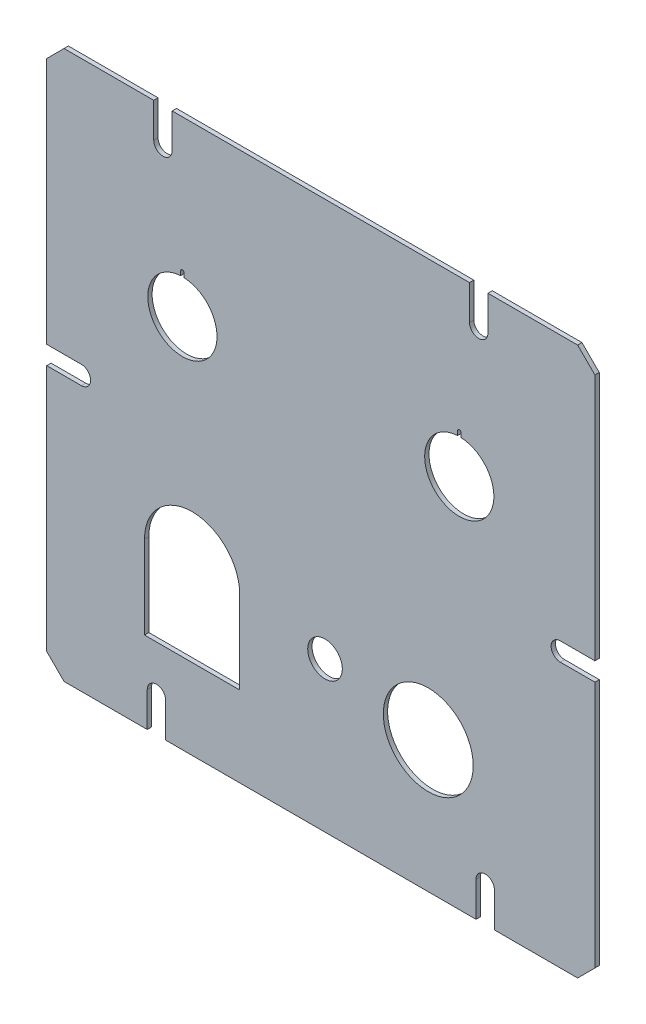
SolidWorks part; units mm, degrees
material "PE High Density"
ref_plane "Front" through (0, 0, 0) normal (0, 0, 1) x (1, 0, 0)
ref_plane "Top" through (0, 0, 0) normal (0, 1, 0) x (1, 0, 0)
ref_plane "Right" through (0, 0, 0) normal (1, 0, 0) x (0, 0, -1)
ref_axis "Axis1" through (0, 0, 55) along (0, 0, -1)
sketch "Sketch1" plane through (0, 0, 0) normal (0, 0, 1) x (1, 0, 0)
  line L1 (-100.584, 100.584) -> (100.584, 100.584)
  line L2 (-100.584, 100.584) -> (-100.584, -100.584)
  line L3 (-100.584, -100.584) -> (100.584, -100.584)
  line L4 (100.584, 100.584) -> (100.584, -100.584)
  line L5 (-100.584, 100.584) -> (100.584, -100.584) construction
  line L6 (-100.584, -100.584) -> (100.584, 100.584) construction
  point P0 (0, 0)
  dimension "D1" = 201.168
extrude "Boss-Extrude1" add sketch "Sketch1" along normal blind 1.5875
sketch "Sketch2" plane through (0, 0, 1.5875) normal (0, 0, 1) x (1, 0, 0)
  line L0 (100.584, -100.584) -> (100.584, 100.584) construction
  line L1 (100.584, 100.584) -> (-100.584, 100.584) construction
  circle A0 centre (-47.244, -40.5765) radius 17.4625
  circle A1 centre (39.4206, -52.284) radius 16.5
  dimension "D1" = 33
  dimension "D6" = 34.925
  dimension "D2" = 61.1634
  dimension "D3" = 147.828
  dimension "D4" = 141.1605
  dimension "D5" = 152.868
extrude "Cut-Extrude1" cut sketch "Sketch2" against normal up to next
hole_wizard "1/4 Clearance Hole1" positions "Sketch3" profile "Sketch4" hole size "1/4" standard "ANSI Inch" end condition up to next
sketch "Sketch3" plane through (0, 0, 1.5875) normal (0, 0, 1) x (1, 0, 0)
  line L0 (0, 100.584) -> (0, -100.584) construction
  line L1 (100.584, 100.584) -> (-100.584, 100.584) construction
  line L2 (-100.584, -100.584) -> (100.584, -100.584) construction
  line L4 (-100.584, 0) -> (100.584, 0) construction
  line L5 (-100.584, 100.584) -> (-100.584, -100.584) construction
  line L6 (100.584, -100.584) -> (100.584, 100.584) construction
  line L8 (-57.9437, 87.884) -> (57.9438, 87.884) construction
  line L10 (-60.325, -87.884) -> (60.325, -87.884) construction
  point P0 (-57.9437, 87.884)
  point P2 (57.9438, 87.884)
  point P4 (87.884, 0)
  point P6 (-87.884, 0)
  point P8 (-60.325, -87.884)
  point P10 (60.325, -87.884)
  dimension "D1" = 12.7
  dimension "D2" = 115.8875
  dimension "D3" = 12.7
  dimension "D4" = 120.65
  dimension "D5" = 12.7
sketch "Sketch4" plane through (-57.9437, 87.884, 1.5875) normal (1, 0, 0) x (0, -1, 0)
  line L0 (0, 0) -> (0, 1.5875)
  line L1 (0, 1.5875) -> (3.3782, 1.5875)
  line L2 (3.3782, 1.5875) -> (3.3782, 0)
  line L5 (3.3782, 0) -> (0, 0)
  line L11 (0, -6.35) -> (0, 107.95) construction
  dimension "Thru Hole Dia." = 6.7564
  dimension "Thru Hole Depth" = 1.5875
chamfer "Chamfer1" distance 6.35 angle 45 4 edges at (-100.584, -100.584, 0.7937) (100.584, -100.584, 0.7937) (100.584, 100.584, 0.7937) (-100.584, 100.584, 0.7937)
sketch "Sketch5" plane through (0, 0, 0) normal (0, 0, -1) x (-1, 0, 0)
  line L0 (29.7815, -40.5765) -> (29.7815, -71.0565)
  line L1 (29.7815, -71.0565) -> (64.7065, -71.0565)
  line L2 (64.7065, -71.0565) -> (64.7065, -40.5765)
  circle A0 centre (47.244, -40.5765) radius 17.4625 construction
  arc A1 (29.7815, -40.5765) -> (64.7065, -40.5765) centre (47.244, -40.5765) ccw
  dimension "D1" = 30.48
extrude "Cut-Extrude3" cut sketch "Sketch5" against normal up to next
sketch "Sketch6" plane through (0, 0, 0) normal (0, 0, -1) x (-1, 0, 0)
  line L0 (-50.8, 37.084) -> (50.8, 37.084) construction
  line L1 (0, 100.584) -> (0, -100.584) construction
  line L2 (-94.234, 100.584) -> (94.234, 100.584) construction
  line L3 (94.234, -100.584) -> (-94.234, -100.584) construction
  line L4 (-50.8, 37.084) -> (-50.8, 51.308) construction
  line L5 (50.8, 37.084) -> (50.8, 51.308) construction
  line L6 (-50.8, 51.308) -> (50.8, 51.308) construction
  line L7 (-50.165, 49.7681) -> (-50.165, 51.308)
  line L8 (51.435, 49.7681) -> (51.435, 51.308)
  line L9 (-51.435, 49.7681) -> (-51.435, 51.308)
  line L10 (50.165, 49.7681) -> (50.165, 51.308)
  line L11 (-51.435, 37.084) -> (-51.435, 51.308) construction
  line L12 (-50.165, 37.084) -> (-50.165, 51.308) construction
  line L13 (50.165, 37.084) -> (50.165, 51.308) construction
  line L14 (51.435, 37.084) -> (51.435, 51.308) construction
  arc A0 (-51.435, 49.7681) -> (-50.165, 49.7681) centre (-50.8, 37.084) ccw
  arc A1 (50.165, 49.7681) -> (51.435, 49.7681) centre (50.8, 37.084) ccw
  arc A2 (-51.435, 51.308) -> (-50.165, 51.308) centre (-50.8, 51.308) cw
  arc A3 (50.165, 51.308) -> (51.435, 51.308) centre (50.8, 51.308) cw
  dimension "D2" = 25.4
  dimension "D1" = 101.6
  dimension "D3" = 63.5
  dimension "D4" = 0.635
  dimension "D6" = 14.224
  dimension "D5" = 0.635
extrude "Cut-Extrude4" cut sketch "Sketch6" against normal up to next
sketch "Sketch7" plane through (0, 0, 0) normal (0, 0, -1) x (-1, 0, 0)
  line L0 (-61.322, 87.884) -> (-54.5656, 87.884) construction
  line L1 (54.5655, 87.884) -> (61.3219, 87.884) construction
  line L2 (-87.884, 3.3782) -> (-87.884, -3.3782) construction
  line L3 (87.884, 3.3782) -> (87.884, -3.3782) construction
  line L4 (-63.7032, -87.884) -> (-56.9468, -87.884) construction
  line L5 (56.9468, -87.884) -> (63.7032, -87.884) construction
  line L7 (-61.322, 87.884) -> (-54.5656, 87.884)
  line L8 (-61.322, 87.884) -> (-61.322, 102.362)
  line L9 (-61.322, 102.362) -> (-54.5656, 102.362)
  line L10 (-54.5656, 87.884) -> (-54.5656, 102.362)
  line L11 (-61.322, 87.884) -> (-54.5656, 102.362) construction
  line L12 (-61.322, 102.362) -> (-54.5656, 87.884) construction
  line L13 (54.5655, 87.884) -> (61.3219, 87.884)
  line L14 (54.5655, 87.884) -> (54.5655, 102.362)
  line L15 (54.5655, 102.362) -> (61.3219, 102.362)
  line L16 (61.3219, 87.884) -> (61.3219, 102.362)
  line L17 (54.5655, 87.884) -> (61.3219, 102.362) construction
  line L18 (54.5655, 102.362) -> (61.3219, 87.884) construction
  line L19 (87.884, 3.3782) -> (102.362, 3.3782)
  line L20 (87.884, 3.3782) -> (87.884, -3.3782)
  line L21 (87.884, -3.3782) -> (102.362, -3.3782)
  line L22 (102.362, 3.3782) -> (102.362, -3.3782)
  line L23 (87.884, 3.3782) -> (102.362, -3.3782) construction
  line L24 (87.884, -3.3782) -> (102.362, 3.3782) construction
  line L25 (56.9468, -87.884) -> (63.7032, -87.884)
  line L26 (56.9468, -87.884) -> (56.9468, -102.362)
  line L27 (56.9468, -102.362) -> (63.7032, -102.362)
  line L28 (63.7032, -87.884) -> (63.7032, -102.362)
  line L29 (56.9468, -87.884) -> (63.7032, -102.362) construction
  line L30 (56.9468, -102.362) -> (63.7032, -87.884) construction
  line L31 (-63.7032, -87.884) -> (-56.9468, -87.884)
  line L32 (-63.7032, -87.884) -> (-63.7032, -102.362)
  line L33 (-63.7032, -102.362) -> (-56.9468, -102.362)
  line L34 (-56.9468, -87.884) -> (-56.9468, -102.362)
  line L35 (-63.7032, -87.884) -> (-56.9468, -102.362) construction
  line L36 (-63.7032, -102.362) -> (-56.9468, -87.884) construction
  line L37 (-87.884, -3.3782) -> (-102.362, -3.3782)
  line L38 (-87.884, -3.3782) -> (-87.884, 3.3782)
  line L39 (-87.884, 3.3782) -> (-102.362, 3.3782)
  line L40 (-102.362, -3.3782) -> (-102.362, 3.3782)
  line L41 (-87.884, -3.3782) -> (-102.362, 3.3782) construction
  line L42 (-87.884, 3.3782) -> (-102.362, -3.3782) construction
  circle A0 centre (-57.9438, 87.884) radius 3.3782 construction
  circle A1 centre (57.9437, 87.884) radius 3.3782 construction
  circle A2 centre (-87.884, 0) radius 3.3782 construction
  circle A3 centre (87.884, 0) radius 3.3782 construction
  circle A4 centre (-60.325, -87.884) radius 3.3782 construction
  circle A5 centre (60.325, -87.884) radius 3.3782 construction
  point P33 (-57.9438, 95.123)
  point P37 (57.9437, 95.123)
  point P41 (95.123, 0)
  point P45 (60.325, -95.123)
  point P49 (-60.325, -95.123)
  point P53 (-95.123, 0)
  dimension "D1" = 14.478
extrude "Cut-Extrude5" cut sketch "Sketch7" against normal up to next
sketch "Sketch8" plane through (0, 0, 0) normal (0, 0, -1) x (-1, 0, 0)
  line L0 (100.584, -3.3782) -> (100.584, -94.234) construction
  line L1 (94.234, -100.584) -> (63.7032, -100.584) construction
  circle A0 centre (-1.5331, -45.5351) radius 6.35
  dimension "D1" = 12.7
  dimension "D2" = 102.1171
  dimension "D3" = 55.0489
extrude "PORT FOR POWER PLUG" cut sketch "Sketch8" against normal up to next
